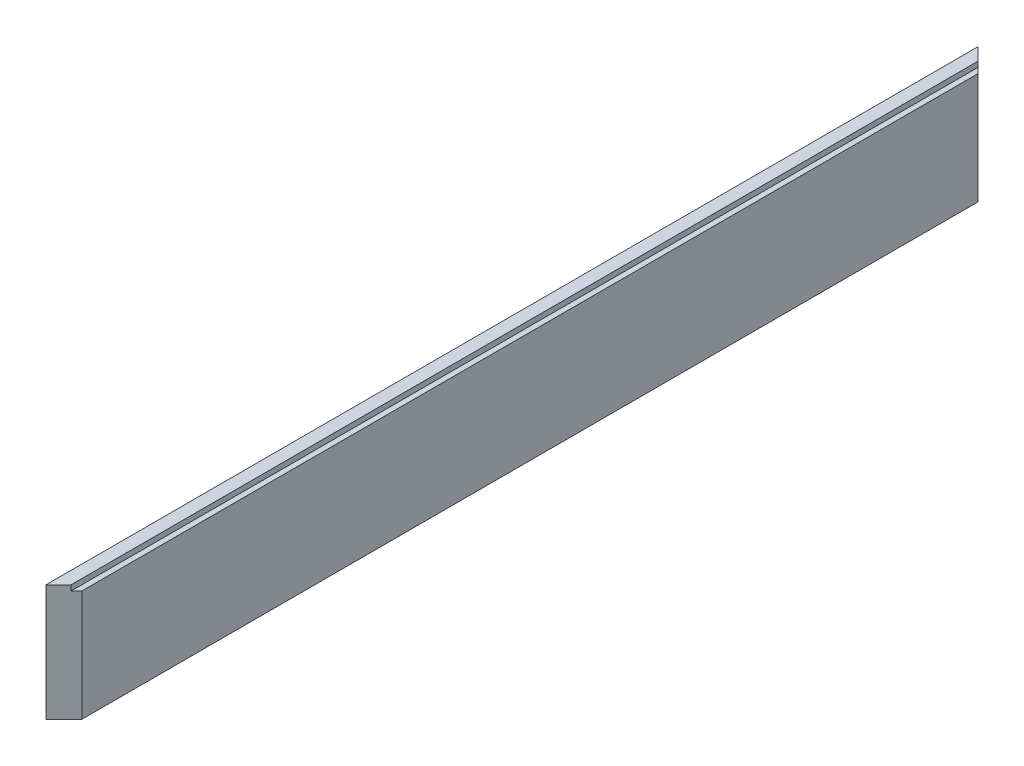
SolidWorks part; units mm, degrees
ref_plane "Plan de face" through (0, 0, 0) normal (0, 0, 1) x (1, 0, 0)
ref_plane "Plan de dessus" through (0, 0, 0) normal (0, 1, 0) x (1, 0, 0)
ref_plane "Plan de droite" through (0, 0, 0) normal (1, 0, 0) x (0, 0, -1)
sketch "Esquisse1" plane through (0, 0, 0) normal (0, 0, 1) x (1, 0, 0)
  line L1 (0, 0) -> (10, 0)
  line L2 (0, 0) -> (0, 65)
  line L3 (0, 65) -> (10, 65)
  line L4 (10, 0) -> (10, 65)
  dimension "D1" = 10
  dimension "D2" = 65
extrude "Boss.-Extru.1" add sketch "Esquisse1" along normal blind 520
chamfer "Chanfrein1" distance 10 angle 45 2 edges at (10, 32.5, 520) (10, 32.5, 0)
sketch "Esquisse2" plane through (0, 0, 0) normal (0, 0, 1) x (1, 0, 0)
  line L1 (10, 65) -> (7, 65)
  line L2 (10, 65) -> (10, 62)
  line L3 (10, 62) -> (7, 62)
  line L4 (7, 65) -> (7, 62)
  dimension "D1" = 3
  dimension "D2" = 3
extrude "Enlèv. mat.-Extru.1" cut sketch "Esquisse2" along normal through all
